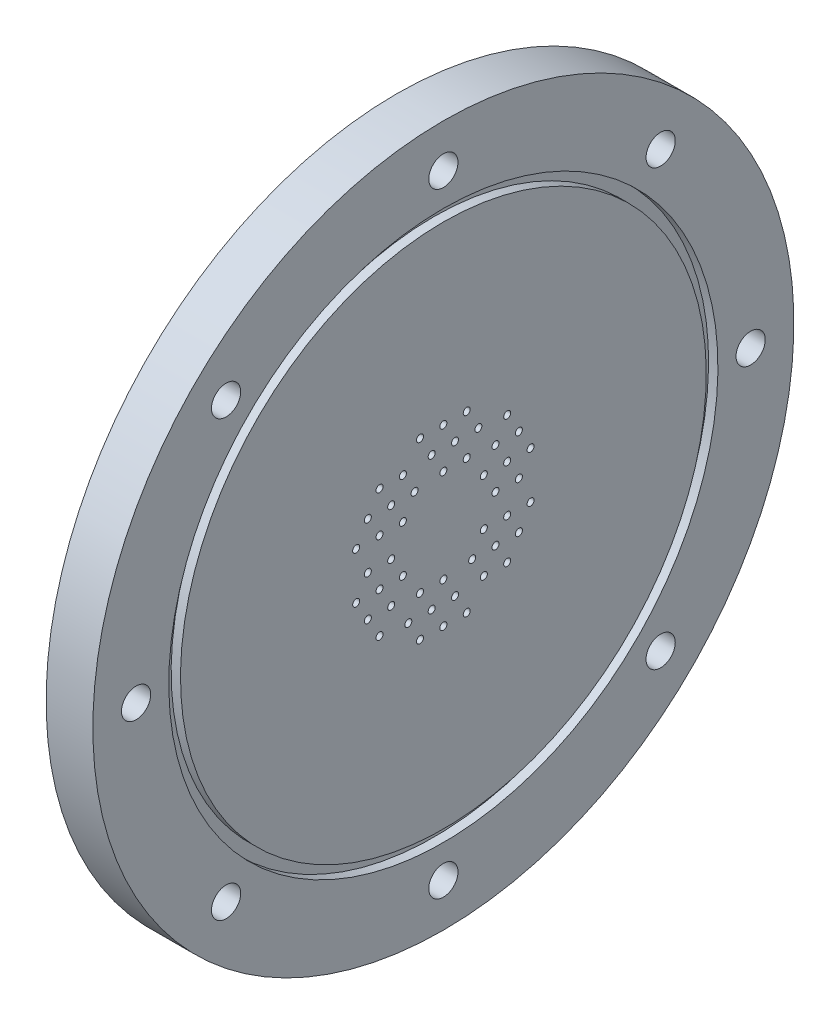
SolidWorks part; units mm, degrees
ref_plane "Front Plane" through (0, 0, 0) normal (0, 0, 1) x (1, 0, 0)
ref_plane "Top Plane" through (0, 0, 0) normal (0, 1, 0) x (1, 0, 0)
ref_plane "Right Plane" through (0, 0, 0) normal (1, 0, 0) x (0, 0, -1)
sketch "Sketch1" plane through (0, 0, 0) normal (0, 0, 1) x (1, 0, 0)
  line L0 (0, 0) -> (0, 48.26)
  line L1 (-2.54, 50.8) -> (-6.35, 50.8)
  line L2 (-6.35, 50.8) -> (-6.35, 76.2)
  line L3 (-6.35, 76.2) -> (3.81, 76.2)
  line L4 (3.81, 76.2) -> (3.81, 0)
  line L5 (3.81, 0) -> (0, 0)
  line L6 (-6.35, 50.8) -> (-6.35, 0) construction
  line L7 (-6.35, 0) -> (0, 0) construction
  arc A0 (0, 48.26) -> (-2.54, 50.8) centre (-2.54, 48.26) ccw
  dimension "Injector Plate Edge Curve" = 2.54
  dimension "Injector Plate Main Thickness" = 3.81
  dimension "Comp" = 152.4
  dimension "Injector Plate Boundry" = 25.4
  dimension "Injector Plate Manifold Height" = 6.35
revolve "Revolve1" add sketch "Sketch1" angle 360 about L7
sketch "Sketch2" plane through (3.81, 0, 0) normal (1, 0, 0) x (0, 0, -1)
  line L0 (0, 10.16) -> (5.08, 10.16) construction
  line L37 (5.08, 10.16) -> (2.54, 14.5594) construction
  line L38 (0, 10.16) -> (-2.54, 14.5594) construction
  line L39 (2.54, 14.5594) -> (0, 10.16) construction
  line L40 (-2.54, 14.5594) -> (2.54, 14.5594) construction
  line L41 (2.54, 14.5594) -> (7.62, 14.5594) construction
  line L42 (7.62, 14.5594) -> (5.08, 10.16) construction
  line L43 (2.54, 14.5594) -> (5.08, 18.9588) construction
  line L44 (5.08, 18.9588) -> (7.62, 14.5594) construction
  line L45 (-2.54, 14.5594) -> (0, 18.9588) construction
  line L46 (0, 18.9588) -> (2.54, 14.5594) construction
  line L47 (0, 18.9588) -> (5.08, 18.9588) construction
  line L48 (-2.54, 14.5594) -> (-5.08, 18.9588) construction
  line L49 (-5.08, 18.9588) -> (0, 18.9588) construction
  circle A3 centre (0, 10.16) radius 0.762
  circle A7 centre (-2.54, 14.5594) radius 0.762
  circle A8 centre (5.08, 10.16) radius 0.762
  circle A9 centre (-5.08, 18.9588) radius 0.762
  circle A10 centre (0, 18.9588) radius 0.762
  circle A11 centre (5.08, 18.9588) radius 0.762
  circle A12 centre (7.62, 14.5594) radius 0.762
  circle A13 centre (2.54, 14.5594) radius 0.762
  dimension "Injector Plate Holes Diameter" = 1.524
  dimension "Distance Between Holes" = 5.08
  dimension "1st Hole Distance from Center" = 10.16
extrude "Cut-Extrude1" cut sketch "Sketch2" against normal through all
chamfer "Chamfer1" distance 0.508 angle 45 8 edges at (0, 10.922, 0) (0, 10.922, -5.08) (0, 15.3214, -7.62) (0, 15.3214, -2.54) (0, 15.3214, 2.54) (0, 19.7208, 5.08) (0, 19.7208, 0) (0, 19.7208, -5.08)
pattern_circular "CirPattern1" count 6 over 360 about axis through (-6.35, 0, 0) along (-1, 0, 0) of "Cut-Extrude1", "Chamfer1" reverse direction yes
sketch "Sketch3" plane through (3.81, 0, 0) normal (1, 0, 0) x (0, 0, -1)
  line L0 (-66.802, 0) -> (0, 0) construction
  circle A0 centre (-66.802, 0) radius 3.175
  dimension "Screw Hole Diameter" = 6.35
  dimension "Injector Plate Screw Hole Distance" = 66.802
extrude "Cut-Extrude2" cut sketch "Sketch3" against normal through all
pattern_circular "CirPattern2" count 8 over 360 about axis through (-6.35, 0, 0) along (-1, 0, 0) of "Cut-Extrude2" reverse direction yes
sketch "Sketch4" plane through (0, 0, 0) normal (0, 0, 1) x (1, 0, 0)
  line L0 (3.81, -76.2) -> (3.81, 76.2) construction
  line L1 (3.81, 59.69) -> (1.778, 59.69)
  line L2 (3.81, 59.69) -> (3.81, 57.15)
  line L3 (3.81, 57.15) -> (1.778, 57.15)
  line L4 (1.778, 59.69) -> (1.778, 57.15)
  line L5 (-6.35, 76.2) -> (-6.35, -76.2) construction
  line L6 (-6.35, 59.69) -> (-4.318, 59.69)
  line L7 (-6.35, 59.69) -> (-6.35, 57.15)
  line L8 (-6.35, 57.15) -> (-4.318, 57.15)
  line L9 (-4.318, 59.69) -> (-4.318, 57.15)
  line L11 (0, 0) -> (-6.35, 0) construction
  line L13 (-6.35, 50.8) -> (-5.08, 50.8)
  line L14 (-6.35, 50.8) -> (-6.35, 53.34)
  line L15 (-6.35, 53.34) -> (-5.08, 53.34)
  line L16 (-5.08, 50.8) -> (-5.08, 53.34)
  dimension "O-Ring Depth" = 2.032
  dimension "O-Ring Width" = 2.54
  dimension "Locater Ring Width" = 2.54
  dimension "Locater Ring Depth" = 1.27
  dimension "O-Ring Radius" = 57.15
revolve "Cut-Revolve1" cut sketch "Sketch4" angle 360 about L11
